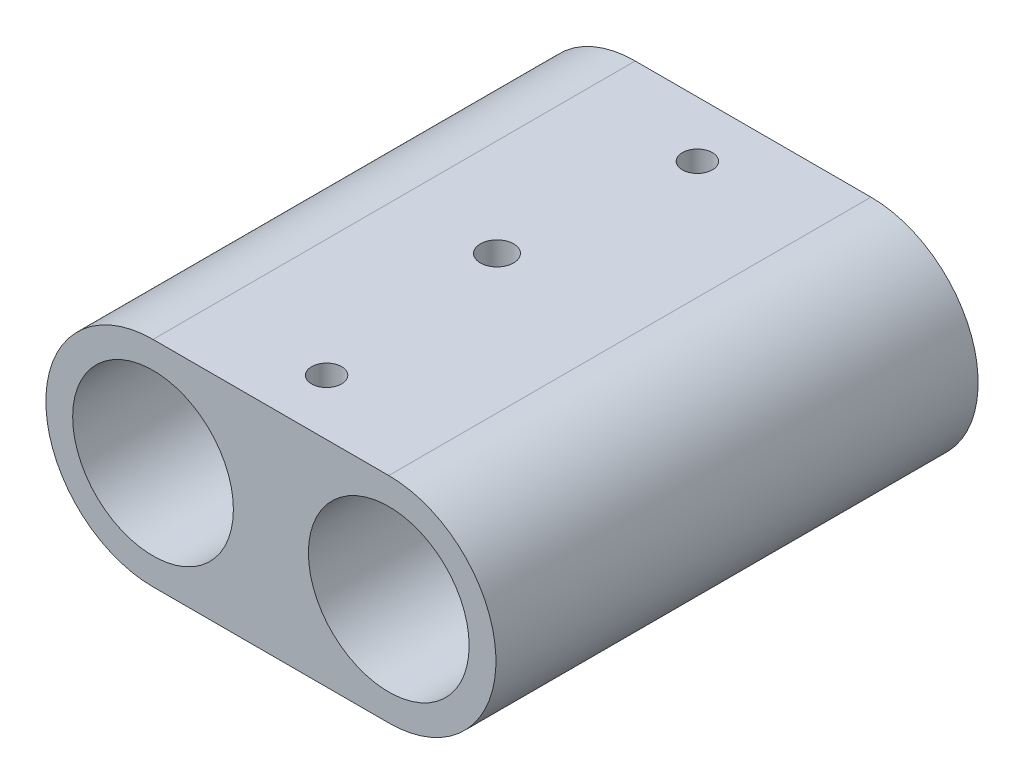
SolidWorks part; units mm, degrees
ref_plane "Front" through (0, 0, 0) normal (0, 0, 1) x (1, 0, 0)
ref_plane "Top" through (0, 0, 0) normal (0, 1, 0) x (1, 0, 0)
ref_plane "Right" through (0, 0, 0) normal (1, 0, 0) x (0, 0, -1)
sketch "Эскиз1" plane through (0, 0, 0) normal (0, 0, 1) x (1, 0, 0)
  line L0 (-11, 10) -> (11, 10)
  line L1 (-11, -10) -> (11, -10)
  circle A2 centre (-11, 0) radius 7.5
  circle A3 centre (11, 0) radius 7.5
  arc A4 (-11, 10) -> (-11, -10) centre (-11, 0) ccw
  arc A5 (11, -10) -> (11, 10) centre (11, 0) ccw
  dimension "D1" = 22
  dimension "D3" = 15
  dimension "D4" = 15
  dimension "D5" = 20
  dimension "D6" = 20
  dimension "D2" = 11
extrude "Бобышка-Вытянуть1" add sketch "Эскиз1" along normal blind 37
sketch "Эскиз6" plane through (0, -10, 0) normal (0, -1, 0) x (1, 0, 0)
  line L2 (-11, 0) -> (11, 0) construction
  line L3 (-11, 37) -> (-11, 0) construction
  circle A0 centre (-1.9, 18) radius 2.75
  dimension "D1" = 9.1
  dimension "D3" = 5.5
  dimension "D2" = 18
extrude "Вырез-Вытянуть3" cut sketch "Эскиз6" against normal blind 5.5
sketch "Эскиз8" plane through (0, -4.5, 0) normal (0, -1, 0) x (1, 0, 0)
  circle A0 centre (-1.9, 18) radius 1.55
extrude "Вырез-Вытянуть6" cut sketch "Эскиз8" against normal through all
chamfer "Фаска1" distance 1.2 angle 45 1 edges at (-0.35, -4.5, 18)
sketch "Эскиз12" plane through (0, -10, 0) normal (0, -1, 0) x (1, 0, 0)
  line L0 (-11, 37) -> (-11, 0) construction
  line L1 (-11, 37) -> (11, 37) construction
  line L3 (11, 37) -> (11, 0) construction
  line L5 (-11, 0) -> (11, 0) construction
  circle A0 centre (-4, 32.5) radius 1.3
  circle A1 centre (4, 4.5) radius 1.3
  dimension "D1" = 7
  dimension "D2" = 4.5
  dimension "D3" = 7
  dimension "D4" = 4.5
extrude "Вырез-Вытянуть8" cut sketch "Эскиз12" against normal blind 5
sketch "Эскиз17" plane through (0, 0, 37) normal (0, 0, 1) x (1, 0, 0)
  line L0 (-11, 10) -> (11, 10)
  line L1 (-11, -10) -> (11, -10)
  arc A0 (-11, 10) -> (-11, -10) centre (-11, 0) ccw
  arc A1 (11, 10) -> (11, -10) centre (11, 0) cw
  circle A2 centre (-11, 0) radius 7.5
  circle A3 centre (11, 0) radius 7.5
extrude "Бобышка-Вытянуть5" add sketch "Эскиз17" along normal blind 4
sketch "Эскиз18" plane through (0, 0, 0) normal (0, 0, -1) x (-1, 0, 0)
  line L0 (-11, 10) -> (11, 10)
  line L1 (-11, -10) -> (11, -10)
  arc A0 (-11, 10) -> (-11, -10) centre (-11, 0) ccw
  arc A1 (11, 10) -> (11, -10) centre (11, 0) cw
  circle A2 centre (-11, 0) radius 7.5
  circle A3 centre (11, 0) radius 7.5
extrude "Бобышка-Вытянуть6" add sketch "Эскиз18" along normal blind 4
sketch "Эскиз19" plane through (0, 10, 0) normal (0, 1, 0) x (1, 0, 0)
  line L0 (0, -41) -> (0, 4) construction
  line L1 (11, -41) -> (-11, -41) construction
  line L2 (-11, 4) -> (11, 4) construction
  line L3 (11, -35.8) -> (-11, -35.8) construction
  line L4 (11, -41) -> (11, 4) construction
  line L5 (-11, -41) -> (-11, 4) construction
  line L6 (11, -1.2) -> (-11, -1.2) construction
  circle A0 centre (0, -1.2) radius 1.4
  circle A1 centre (0, -35.8) radius 1.4
  dimension "D1" = 5.2
  dimension "D2" = 5.2
extrude "Вырез-Вытянуть12" cut sketch "Эскиз19" against normal through all
sketch "Эскиз20" plane through (0, -10, 0) normal (0, -1, 0) x (-1, 0, 0)
  circle A0 centre (0, -35.8) radius 2.75
  circle A1 centre (0, -1.2) radius 2.75
extrude "Вырез-Вытянуть14" cut sketch "Эскиз20" against normal blind 3
sketch "Эскиз21" plane through (0, -10, 0) normal (0, -1, 0) x (1, 0, 0)
  line L0 (-2.7, 32.5) -> (-11, 32.5) construction
  line L1 (-11, 41) -> (-11, -4) construction
  line L2 (5.3, 4.5) -> (-11, 4.5) construction
  line L3 (-4.65, 18) -> (-14.6461, 18) construction
  line L4 (0, 1.2) -> (0, 35.8) construction
  circle A0 centre (-4, 32.5) radius 1.3 construction
  circle A1 centre (4, 4.5) radius 1.3 construction
  circle A2 centre (-1.9, 18) radius 2.75 construction
  dimension "D1" = 28
